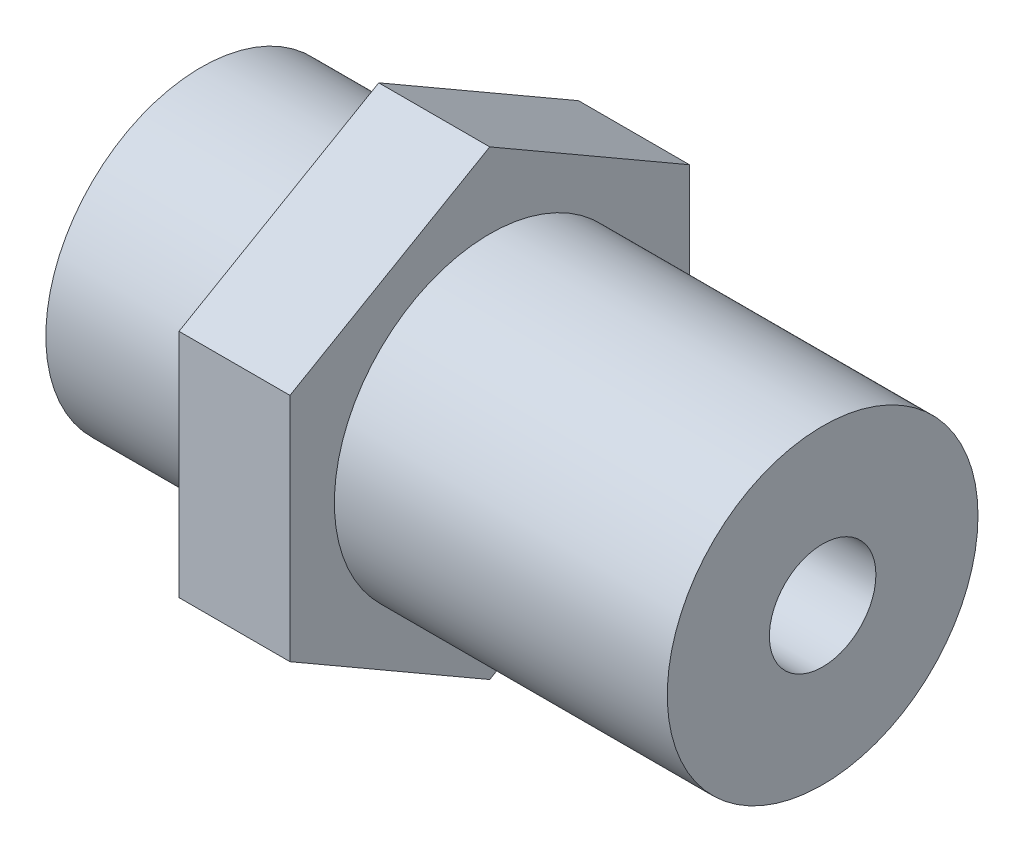
SolidWorks part; units mm, degrees
material "6061-T6 (SS)"
ref_plane "Alzado" through (0, 0, 0) normal (0, 0, 1) x (1, 0, 0)
ref_plane "Planta" through (0, 0, 0) normal (0, 1, 0) x (1, 0, 0)
ref_plane "Vista lateral" through (0, 0, 0) normal (1, 0, 0) x (0, 0, -1)
ref_plane "Plano2" through (-32, 0, 0) normal (1, 0, 0) x (0, 0, -1)
sketch "Sk_barril" plane through (-32, 0, 0) normal (1, 0, 0) x (0, 0, -1)
  circle A0 centre (-60.4, -16) radius 3.5
  circle A1 centre (-60.4, -16) radius 1.2
extrude "Barril" add sketch "Sk_barril" against normal blind 14 from offset 2
ref_plane "Plano4" through (-40, 0, 0) normal (1, 0, 0) x (0, 0, -1)
sketch "Sk_contratuerca" plane through (-40, 0, 0) normal (1, 0, 0) x (0, 0, -1)
  line L0 (-60.4, -10.8038) -> (-64.9, -13.4019)
  line L1 (-64.9, -13.4019) -> (-64.9, -18.5981)
  line L2 (-64.9, -18.5981) -> (-60.4, -21.1962)
  line L3 (-60.4, -21.1962) -> (-55.9, -18.5981)
  line L4 (-55.9, -18.5981) -> (-55.9, -13.4019)
  line L5 (-55.9, -13.4019) -> (-60.4, -10.8038)
  circle A0 centre (-60.4, -16) radius 1.2
extrude "Contratuerca" add sketch "Sk_contratuerca" along normal blind 2.5
